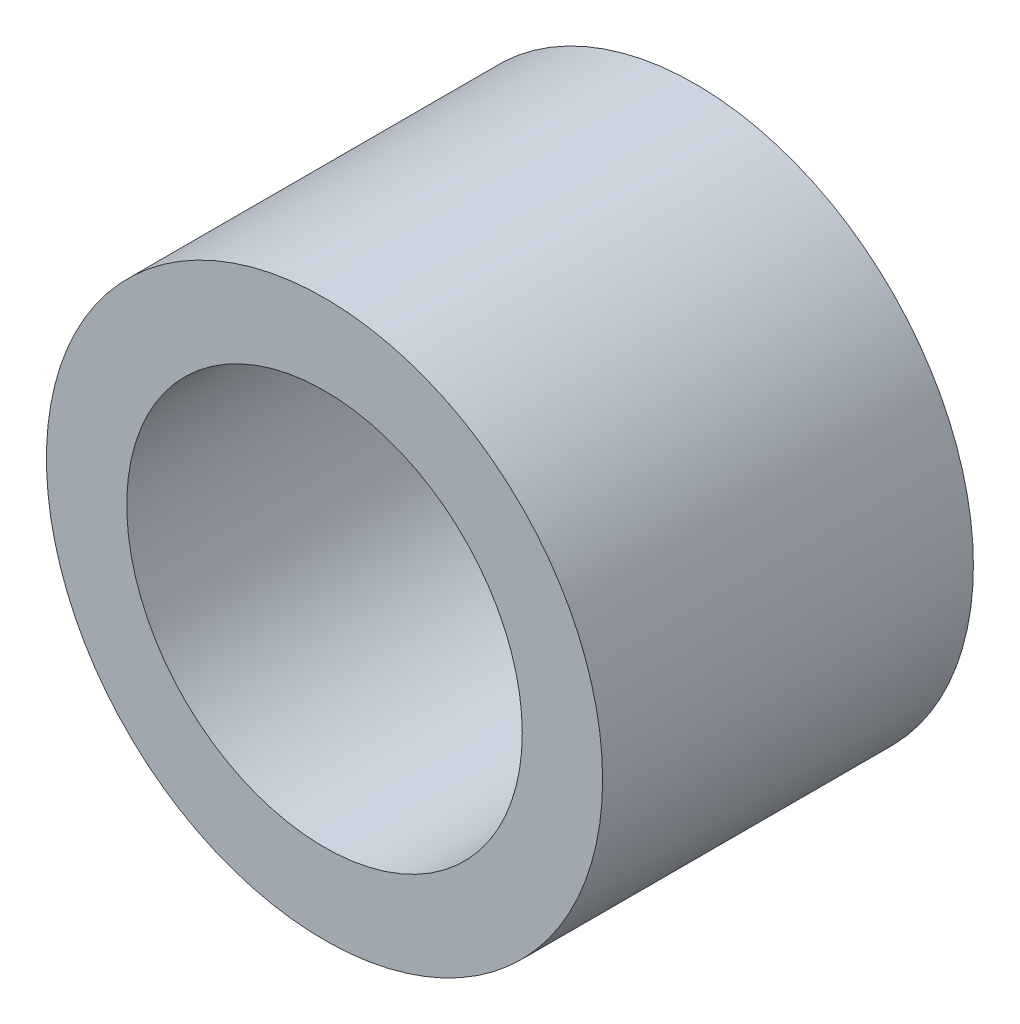
SolidWorks part; units mm, degrees
ref_plane "Front Plane" through (0, 0, 0) normal (0, 0, 1) x (1, 0, 0)
ref_plane "Top Plane" through (0, 0, 0) normal (0, 1, 0) x (1, 0, 0)
ref_plane "Right Plane" through (0, 0, 0) normal (1, 0, 0) x (0, 0, -1)
sketch "Sketch1" plane through (0, 0, 0) normal (0, 0, 1) x (1, 0, 0)
  circle A0 centre (0, 0) radius 2.25
  circle A1 centre (0, 0) radius 1.6
  dimension "OD" = 4.5
  dimension "ID" = 3.2
extrude "Extrude1" add sketch "Sketch1" along normal mid plane 3
sketch "Sketch2" plane through (0, 0, 0) normal (1, 0, 0) x (0, 0, -1)
  line L0 (-1.5, -1.6) -> (1.5, -1.6) construction
  line L3 (1.5, 1.6) -> (-1.5, 1.6) construction
  line L5 (-1.5, -1.6) -> (1.5, -1.6)
  line L6 (1.5, 1.6) -> (-1.5, 1.6)
sketch "Sketch4" plane through (0, 0, 1.5) normal (0, 0, 1) x (1, 0, 0)
  line L0 (0, 0) -> (-1.1314, 1.1314)
  line L1 (0, -1.1) -> (0, 1.1) construction
  circle A0 centre (0, 0) radius 1.6 construction
  dimension "D1" = 45
